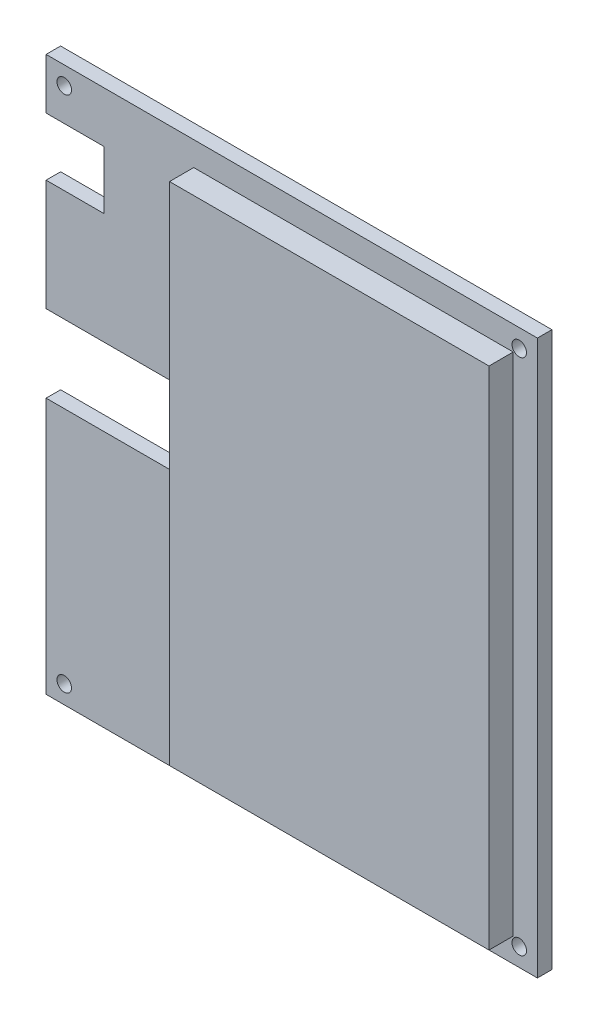
SolidWorks part; units mm, degrees
ref_plane "Front Plane" through (0, 0, 0) normal (0, 0, 1) x (1, 0, 0)
ref_plane "Top Plane" through (0, 0, 0) normal (0, 1, 0) x (1, 0, 0)
ref_plane "Right Plane" through (0, 0, 0) normal (1, 0, 0) x (0, 0, -1)
sketch "Sketch1" plane through (0, 0, 0) normal (0, 0, 1) x (-1, 0, 0)
  line L0 (50.75, 10.25) -> (50.75, 48.25)
  line L1 (-50.75, -41.25) -> (-50.75, -14.25)
  line L2 (-50.75, -14.25) -> (-50.7359, -14.3661)
  line L3 (29.75, -57.25) -> (-43.25, -57.25)
  line L4 (-43.25, -57.25) -> (-43.462, -57.4644)
  line L5 (50.75, -29.75) -> (50.75, -20.75)
  line L123 (14.75, -57.25) -> (21.75, -57.25)
  line L127 (29.75, -57.25) -> (50.75, -57.25)
  line L128 (50.75, -57.25) -> (50.75, -46.75)
  line L129 (50.75, -46.75) -> (38.75, -46.75)
  line L130 (38.75, -46.75) -> (38.75, -34.75)
  line L131 (38.75, -34.75) -> (50.75, -34.75)
  line L132 (50.75, -34.75) -> (50.75, -29.75)
  line L136 (50.75, -20.75) -> (50.75, -11.75)
  line L137 (50.75, -11.75) -> (25.25, -11.75)
  line L138 (25.25, -11.75) -> (25.25, 4.25)
  line L139 (25.25, 4.25) -> (50.75, 4.25)
  line L140 (50.75, 4.25) -> (50.75, 10.25)
  line L144 (50.75, 25.25) -> (50.75, 33.25)
  line L148 (50.75, 48.25) -> (50.75, 57.25)
  line L149 (50.75, 57.25) -> (-50.75, 57.25)
  line L150 (-50.75, 57.25) -> (-50.75, -14.25)
  line L154 (-50.75, -41.25) -> (-50.75, -57.25)
  line L155 (-50.75, -57.25) -> (-43.25, -57.25)
  line L159 (-13.25, -57.25) -> (-5.25, -57.25)
  circle A8 centre (-47, -53.5) radius 1.5
  circle A11 centre (-47, 53.5) radius 1.5
  circle A14 centre (47, 53.5) radius 1.5
  circle A17 centre (47, -53.5) radius 1.5
extrude "Boss-Extrude1" add sketch "Sketch1" along normal blind 3 contours L154 L155 L3 L127 L128 L129 L130 L131 L132 L5 L136 L137 L138 L139 L140 L0 L148 L149 L150 L1 A17 A14 A11 A8 region at (1.9878, -0.67, 0)
sketch "Sketch2" plane through (0, 0, 0) normal (0, 0, -1) x (-1, 0, 0)
  line L0 (-50.75, -57.25) -> (-50.75, 57.25) construction
  line L1 (20.25, -52.25) -> (-45.75, -52.25)
  line L2 (20.25, -52.25) -> (20.25, 52.25)
  line L3 (20.25, 52.25) -> (-45.75, 52.25)
  line L4 (-45.75, -52.25) -> (-45.75, 52.25)
  line L5 (20.25, -52.25) -> (-45.75, 52.25) construction
  line L6 (0, 0) -> (-12.75, 0) construction
  line L7 (50.75, -57.25) -> (-50.75, -57.25) construction
  line L8 (25.25, 11.75) -> (25.25, -4.25) construction
  point P0 (0, 0)
  dimension "D1" = 5
  dimension "D2" = 5
  dimension "D3" = 5
extrude "Boss-Extrude2" add sketch "Sketch2" against normal blind 8
